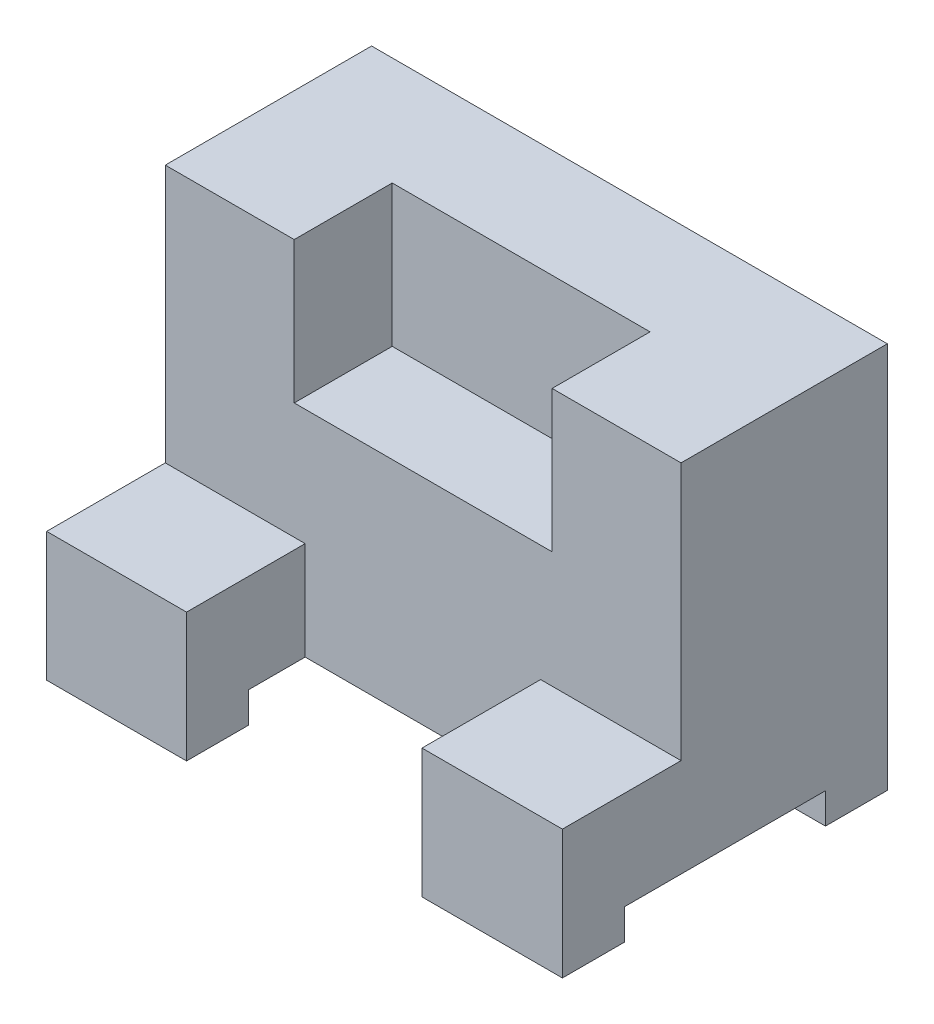
SolidWorks part; units mm, degrees
ref_plane "Front Plane" through (0, 0, 0) normal (0, 0, 1) x (1, 0, 0)
ref_plane "Top Plane" through (0, 0, 0) normal (0, 1, 0) x (1, 0, 0)
ref_plane "Right Plane" through (0, 0, 0) normal (1, 0, 0) x (0, 0, -1)
sketch "Sketch1" plane through (0, 0, 0) normal (0, 0, 1) x (1, 0, 0)
  line L1 (0, 0) -> (100, 0)
  line L2 (0, 0) -> (0, 75)
  line L3 (0, 75) -> (100, 75)
  line L4 (100, 0) -> (100, 75)
  line L5 (0, 0) -> (27.1204, 0)
  line L6 (0, 0) -> (0, 25)
  line L7 (0, 25) -> (27.1204, 25)
  line L8 (27.1204, 0) -> (27.1204, 25)
  line L9 (100, 0) -> (72.7749, 0)
  line L10 (100, 0) -> (100, 25)
  line L11 (100, 25) -> (72.7749, 25)
  line L12 (72.7749, 0) -> (72.7749, 25)
  line L13 (25, 75) -> (75, 75)
  line L14 (25, 75) -> (25, 47.5654)
  line L15 (25, 47.5654) -> (75, 47.5654)
  line L16 (75, 75) -> (75, 47.5654)
  dimension "D1" = 100
  dimension "D2" = 50
  dimension "D3" = 25
  dimension "D4" = 25
  dimension "D5" = 25
  dimension "D6" = 75
extrude "Boss-Extrude2" add sketch "Sketch1" along normal blind 63 contours L1 L8 L7 L2 | L12 L1 L4 L11 region at (13.5602, 12.5, 0) region at (86.3874, 12.5, 0)
extrude "Boss-Extrude3" add sketch "Sketch1<5>" along normal blind 40 contours L3 L16 L15 L14 L2 L7 L8 L1 L12 L11 L4 region at (49.9875, 37.7815, 0)
sketch "Sketch1<5>" plane through (0, 0, 0) normal (0, 0, 1) x (1, 0, 0) same geometry as "Sketch1"
extrude "Boss-Extrude4" add sketch "Sketch1<6>" along normal blind 40 contours L16 L3 L14 L15 region at (50, 61.2827, 0)
sketch "Sketch1<6>" plane through (0, 0, 0) normal (0, 0, 1) x (1, 0, 0) same geometry as "Sketch1"
extrude "Cut-Extrude1" cut sketch "Sketch1<7>" against normal blind 19 from surface contours L16 L3 L14 L15 region at (50, 61.2827, 0) starting at face at (49.9738, 31.25, 40)
sketch "Sketch1<7>" plane through (0, 0, 0) normal (0, 0, 1) x (1, 0, 0) same geometry as "Sketch1"
sketch "Sketch2" plane through (0, 0, 0) normal (-1, 0, 0) x (0, 0, 1)
  line L0 (63, 0) -> (0, 0) construction
  line L1 (12, 0) -> (51, 0)
  line L2 (12, 0) -> (12, 5.9469)
  line L3 (12, 5.9469) -> (51, 5.9469)
  line L4 (51, 0) -> (51, 5.9469)
  dimension "D1" = 39
  dimension "D2" = 12
extrude "Cut-Extrude2" cut sketch "Sketch2" against normal through all
